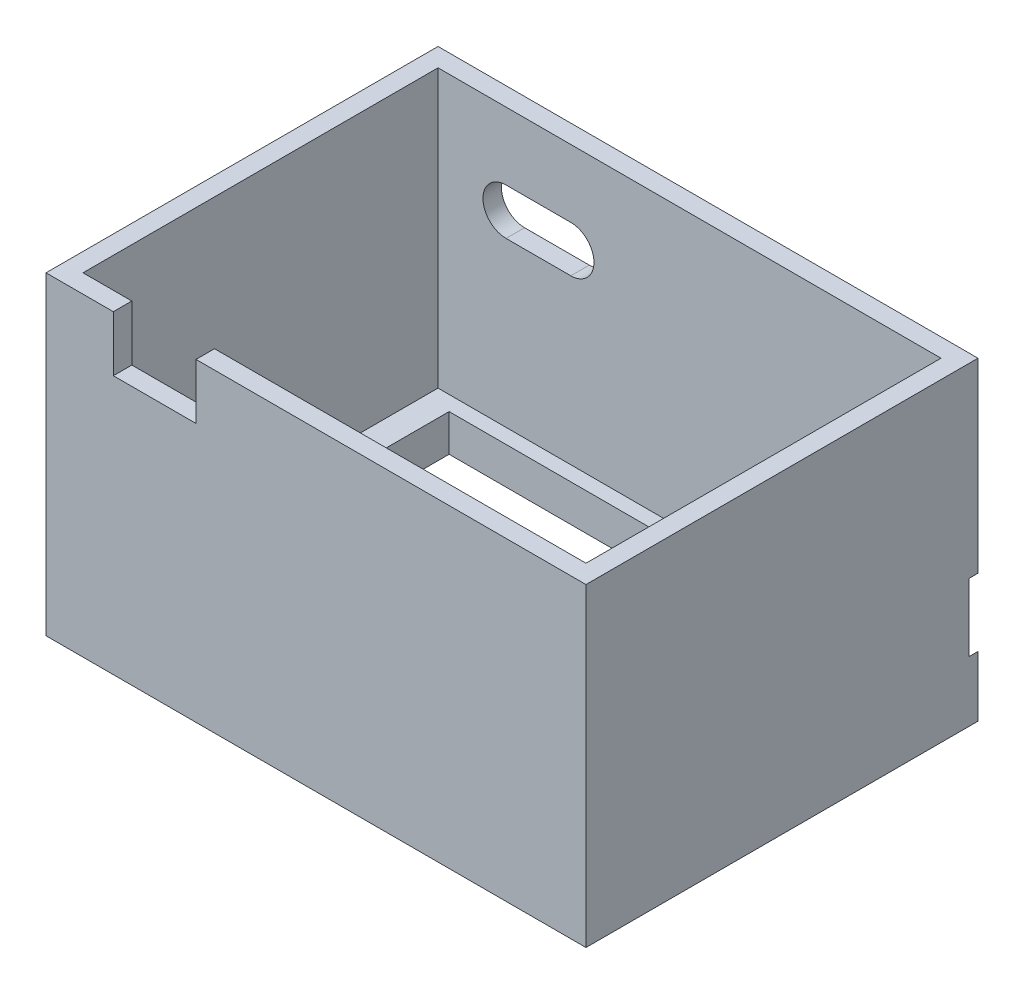
SolidWorks part; units mm, degrees
ref_plane "前视基准面" through (0, 0, 0) normal (0, 0, 1) x (1, 0, 0)
ref_plane "上视基准面" through (0, 0, 0) normal (0, 1, 0) x (1, 0, 0)
ref_plane "右视基准面" through (0, 0, 0) normal (1, 0, 0) x (0, 0, -1)
sketch "草图1" plane through (0, 0, 0) normal (0, 1, 0) x (1, 0, 0)
  line L1 (-69.1759, -29.4797) -> (-39.9759, -29.4797)
  line L2 (-69.1759, -29.4797) -> (-69.1759, -8.2797)
  line L3 (-69.1759, -8.2797) -> (-39.9759, -8.2797)
  line L4 (-39.9759, -29.4797) -> (-39.9759, -8.2797)
extrude "凸台-拉伸1" add sketch "草图1" along normal blind 17 contours L2 L1 L4 L3
sketch "草图2" plane through (0, 17, 0) normal (0, 1, 0) x (1, 0, 0)
  line L0 (-39.9759, -29.4797) -> (-39.9759, -8.2797) construction
  line L1 (-68.1759, -9.2797) -> (-40.9759, -9.2797)
  line L2 (-68.1759, -9.2797) -> (-68.1759, -28.4797)
  line L3 (-68.1759, -28.4797) -> (-40.9759, -28.4797)
  line L4 (-40.9759, -9.2797) -> (-40.9759, -28.4797)
  line L5 (-69.1759, -29.4797) -> (-39.9759, -29.4797) construction
  line L6 (-69.1759, -29.4797) -> (-69.1759, -8.2797) construction
  dimension "D1" = 1
  dimension "D2" = 1
  dimension "D3" = 1
extrude "切除-拉伸1" cut sketch "草图2" against normal blind 15
sketch "草图4" plane through (0, 0, 0) normal (0, -1, 0) x (-1, 0, 0)
  line L0 (69.1759, -29.4797) -> (69.1759, -8.2797) construction
  line L1 (66.7759, -10.0797) -> (49.1759, -10.0797)
  line L2 (66.7759, -10.0797) -> (66.7759, -27.6797)
  line L3 (66.7759, -27.6797) -> (49.1759, -27.6797)
  line L4 (49.1759, -10.0797) -> (49.1759, -27.6797)
  line L6 (69.1759, -29.4797) -> (39.9759, -29.4797) construction
  dimension "D1" = 17.6
  dimension "D2" = 17.6
  dimension "D3" = 2.4
  dimension "D4" = 1.8
extrude "切除-拉伸2" cut sketch "草图4" against normal blind 15 contours L2 L1 L4 L3
sketch "草图5" plane through (0, 0, 8.2797) normal (0, 0, -1) x (-1, 0, 0)
  line L0 (69.1759, 0) -> (39.9759, 0) construction
  line L6 (64.4959, 12.1) -> (60.9959, 12.1) construction
  line L7 (64.4959, 10.85) -> (60.9959, 10.85)
  line L8 (64.4959, 13.35) -> (60.9959, 13.35)
  line L9 (69.1759, 17) -> (69.1759, 0) construction
  arc A0 (64.4959, 10.85) -> (64.4959, 13.35) centre (64.4959, 12.1) ccw
  arc A1 (60.9959, 13.35) -> (60.9959, 10.85) centre (60.9959, 12.1) ccw
  point P10 (62.7459, 12.1)
  dimension "D3" = 10.85
  dimension "D2" = 2.5
  dimension "D1" = 4.68
  dimension "D4" = 3.5
extrude "切除-拉伸3" cut sketch "草图5" against normal blind 15
sketch "草图6" plane through (0, 0, 29.4797) normal (0, 0, 1) x (1, 0, 0)
  line L0 (-69.1759, 0) -> (-39.9759, 0) construction
  line L1 (-61.0649, 14) -> (-65.534, 14)
  line L2 (-61.0649, 14) -> (-61.0649, 17)
  line L3 (-61.0649, 17) -> (-65.534, 17)
  line L4 (-65.534, 14) -> (-65.534, 17)
  point P6 (-63.2994, 14)
  dimension "D1" = 14
  dimension "D2" = 3
extrude "切除-拉伸4" cut sketch "草图6" against normal blind 5
sketch "草图7" plane through (0, 0, 8.2797) normal (0, 0, -1) x (-1, 0, 0)
  line L3 (49.2759, 5.1) -> (43.0759, 5.1) construction
  line L4 (49.2759, 1.5) -> (43.0759, 1.5)
  line L5 (49.2759, 8.7) -> (43.0759, 8.7)
  arc A2 (49.2759, 1.5) -> (49.2759, 8.7) centre (49.2759, 5.1) ccw
  arc A3 (43.0759, 8.7) -> (43.0759, 1.5) centre (43.0759, 5.1) ccw
  point P10 (46.1759, 5.1)
  point P15 (46.1759, 8.7)
  point P17 (39.4759, 5.1)
  dimension "D3" = 6.2
  dimension "D4" = 7.2
extrude "切除-拉伸7" cut sketch "草图7" against normal blind 0.5
sketch "草图9" plane through (0, 0, 8.7797) normal (0, 0, -1) x (-1, 0, 0)
  line L0 (49.2759, 5.1) -> (43.4759, 5.1) construction
  line L1 (49.2759, 3.5) -> (43.4759, 3.5)
  line L2 (49.2759, 6.7) -> (43.4759, 6.7)
  line L3 (49.2759, 8.7) -> (43.0759, 8.7) construction
  arc A0 (49.2759, 3.5) -> (49.2759, 6.7) centre (49.2759, 5.1) ccw
  arc A1 (43.4759, 6.7) -> (43.4759, 3.5) centre (43.4759, 5.1) ccw
  arc A2 (49.2759, 1.5) -> (49.2759, 8.7) centre (49.2759, 5.1) ccw construction
  point P2 (46.3759, 5.1)
  point P12 (52.8759, 5.1)
  point P13 (50.8759, 5.1)
  point P14 (41.8759, 5.1)
  dimension "D1" = 2
  dimension "D2" = 2
  dimension "D3" = 3.2
  dimension "D4" = 9
extrude "切除-拉伸8" cut sketch "草图9" against normal blind 0.5
